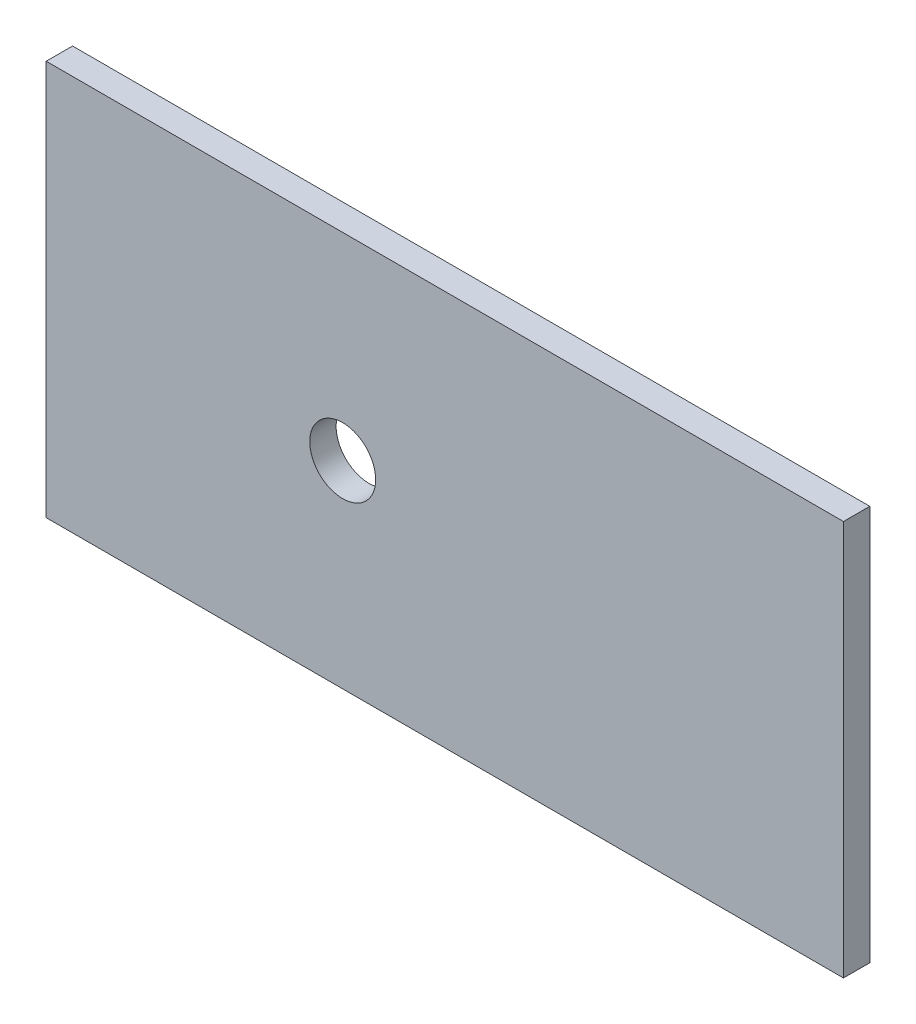
SolidWorks part; units mm, degrees
ref_plane "Front Plane" through (0, 0, 0) normal (0, 0, 1) x (1, 0, 0)
ref_plane "Top Plane" through (0, 0, 0) normal (0, 1, 0) x (1, 0, 0)
ref_plane "Right Plane" through (0, 0, 0) normal (1, 0, 0) x (0, 0, -1)
sketch "Sketch1" plane through (0, 0, 0) normal (0, 0, 1) x (1, 0, 0)
  line L1 (-81, -30) -> (40, -30)
  line L2 (-81, -30) -> (-81, 30)
  line L3 (-81, 30) -> (40, 30)
  line L11 (40, 30) -> (40, -30)
  circle A3 centre (-36, 0) radius 5
  point P9 (-81, 0)
  dimension "D3" = 121
  dimension "D6" = 10
  dimension "D2" = 60
  dimension "D10" = 0
  dimension "D11" = 45
extrude "Boss-Extrude1" add sketch "Sketch1" along normal blind 4
